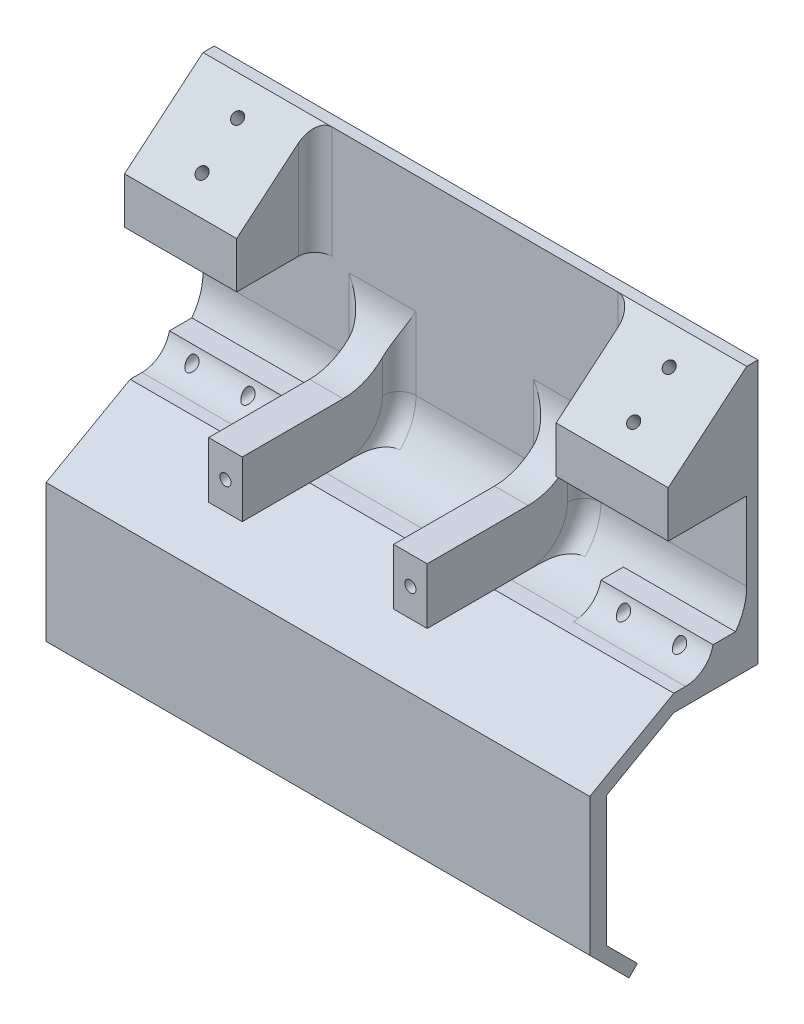
SolidWorks part; units mm, degrees
ref_plane "Front" through (0, 0, 0) normal (0, 0, 1) x (1, 0, 0)
ref_plane "Top" through (0, 0, 0) normal (0, 1, 0) x (1, 0, 0)
ref_plane "Right" through (0, 0, 0) normal (1, 0, 0) x (0, 0, -1)
sketch "Sketch1" plane through (0, 0, 0) normal (0, 0, 1) x (1, 0, 0)
  line L1 (0, 0) -> (97, 0)
  line L2 (0, 0) -> (0, 47)
  line L3 (0, 47) -> (97, 47)
  line L4 (97, 0) -> (97, 47)
  dimension "D1" = 97
  dimension "D2" = 47
extrude "Boss-Extrude1" add sketch "Sketch1" along normal blind 2
sketch "Sketch2" plane through (0, 0, 2) normal (0, 0, 1) x (1, 0, 0)
  line L0 (97, 0) -> (97, 47) construction
  line L1 (0, 47) -> (97, 47)
  line L2 (0, 47) -> (0, 27)
  line L3 (0, 27) -> (97, 27)
  line L4 (97, 47) -> (97, 27)
  dimension "D1" = 20
extrude "Boss-Extrude2" add sketch "Sketch2" along normal blind 20
sketch "Sketch3" plane through (0, 0, 0) normal (-1, 0, 0) x (0, 0, 1)
  line L0 (2, 47) -> (24.809, 27.8609)
  line L1 (22, 47) -> (0, 47) construction
  line L2 (24.809, 27.8609) -> (24.9418, 51.5997)
  line L3 (24.9418, 51.5997) -> (2, 47)
  line L5 (0, 47) -> (0, 0) construction
  dimension "D1" = 50
extrude "Cut-Extrude1" cut sketch "Sketch3" against normal blind 131
sketch "Sketch4" plane through (0, 0, 0) normal (-1, 0, 0) x (0, 0, 1)
  line L0 (19.0479, 32.6951) -> (21.146, 30.9346)
  line L1 (2, 47) -> (22, 30.218) construction
  line L2 (21.146, 30.9346) -> (25.8351, 27)
  line L3 (25.8351, 27) -> (20.0969, 27)
  line L4 (22, 27) -> (2, 27) construction
  line L5 (20.0969, 27) -> (19.0479, 32.6951)
extrude "Boss-Extrude3" add sketch "Sketch4" against normal up to surface (97 mm away) up to face at (97, 25.4597, 7.1429)
sketch "Sketch6" plane through (0, 0, 2) normal (0, 0, 1) x (1, 0, 0)
  line L0 (97, 47) -> (0, 47) construction
  line L1 (20, 47) -> (77, 47)
  line L2 (20, 47) -> (20, 18.3699)
  line L3 (20, 18.3699) -> (77, 18.3699)
  line L4 (77, 47) -> (77, 18.3699)
  line L5 (97, 47) -> (97, 27) construction
  line L6 (0, 47) -> (0, 27) construction
  dimension "D1" = 20
  dimension "D2" = 20
extrude "Cut-Extrude3" cut sketch "Sketch6" along normal blind 82
sketch "Sketch7" plane through (0, 0, 2) normal (0, 0, 1) x (1, 0, 0)
  line L0 (97, 0) -> (97, 27) construction
  line L1 (0, 0) -> (97, 0) construction
  circle A0 centre (15, 5) radius 1
  circle A1 centre (5, 5) radius 1
  circle A2 centre (92, 5) radius 1
  circle A3 centre (82, 5) radius 1
  dimension "D1" = 2
  dimension "D2" = 2
  dimension "D3" = 5
  dimension "D4" = 5
  dimension "D5" = 5
  dimension "D6" = 10
extrude "Cut-Extrude4" cut sketch "Sketch7" against normal blind 82
sketch "Sketch8" plane through (0, 0, 0) normal (-1, 0, 0) x (0, 0, 1)
  line L1 (16, 27) -> (34.739, 27)
  line L2 (16, 27) -> (16, 52.0421)
  line L3 (16, 52.0421) -> (34.739, 52.0421)
  line L4 (34.739, 27) -> (34.739, 52.0421)
  line L5 (2, 27) -> (2, 0) construction
  point P6 (0, 0)
  dimension "D1" = 14
extrude "Cut-Extrude5" cut sketch "Sketch8" against normal blind 136
sketch "Sketch9" plane through (0, 28.5655, 23.9693) normal (0, 0.766, 0.6428) x (1, 0, 0)
  line L0 (20, 28.6789) -> (0, 28.6789) construction
  line L1 (0, 10.4032) -> (20, 10.4032) construction
  circle A0 centre (10, 23.6789) radius 1
  circle A1 centre (10, 15.4032) radius 1
  circle A2 centre (87, 15.4032) radius 1
  circle A3 centre (87, 23.6789) radius 1
  point P12 (10, 28.6789)
  dimension "D3" = 2
  dimension "D4" = 2
  dimension "D1" = 5
  dimension "D2" = 5
extrude "Cut-Extrude6" cut sketch "Sketch9" against normal blind 6
sketch "Sketch11" plane through (0, 0, 2) normal (0, 0, 1) x (1, 0, 0)
  line L1 (0, 0) -> (97, 0)
  line L2 (0, 0) -> (0, 3)
  line L3 (0, 3) -> (97, 3)
  line L4 (97, 0) -> (97, 3)
  point P9 (97, 0)
  dimension "D1" = 3
extrude "Boss-Extrude4" add sketch "Sketch11" along normal blind 13
sketch "Sketch12" plane through (0, 0, 0) normal (-1, 0, 0) x (0, 0, 1)
  line L0 (15, 0) -> (27, -6.7563)
  line L1 (27, -6.7563) -> (32.3283, -6.7563)
  line L2 (32.3283, -6.7563) -> (15, 3)
  line L3 (15, 3) -> (15, 0)
  line L4 (0, 47) -> (0, 0) construction
  dimension "D1" = 27
extrude "Boss-Extrude5" add sketch "Sketch12" against normal up to vertex (97 mm away) up to point (97, 3, 2)
sketch "Sketch13" plane through (0, 0, 0) normal (-1, 0, 0) x (0, 0, 1)
  line L1 (27, -6.7563) -> (30, -6.7563)
  line L2 (27, -6.7563) -> (27, -30)
  line L3 (27, -30) -> (30, -30)
  line L4 (30, -6.7563) -> (30, -30)
  dimension "D1" = 3
  dimension "D2" = 30
extrude "Boss-Extrude6" add sketch "Sketch13" against normal up to vertex (97 mm away) up to point (97, 3, 15)
sketch "Sketch14" plane through (0, 0, 0) normal (-1, 0, 0) x (0, 0, 1)
  line L0 (30, -30) -> (30, -6.7563) construction
  line L1 (30, -11.4573) -> (34.8186, -11.4573)
  line L2 (30, -11.4573) -> (30, -0.9956)
  line L3 (30, -0.9956) -> (34.8186, -0.9956)
  line L4 (34.8186, -11.4573) -> (34.8186, -0.9956)
extrude "Cut-Extrude7" cut sketch "Sketch14" against normal up to vertex (97 mm away) up to point (97, 3, 15)
sketch "Sketch15" plane through (0, 0, 0) normal (-1, 0, 0) x (0, 0, 1)
  line L0 (30, -30) -> (23, -37)
  line L1 (23, -37) -> (21.5, -35.5)
  line L2 (21.5, -35.5) -> (27, -30)
  line L3 (27, -6.7563) -> (27, -30) construction
  line L4 (30, -30) -> (27, -30)
  line L17 (30, -30) -> (30, -5.4454)
  line L18 (30, -5.4454) -> (15, 3)
  line L19 (15, 3) -> (2, 3)
  line L20 (2, 3) -> (2, 27)
  line L21 (2, 27) -> (16, 27)
  line L22 (16, 27) -> (16, 35.2526)
  line L23 (16, 35.2526) -> (2, 47)
  line L24 (2, 47) -> (0, 47)
  line L25 (0, 47) -> (0, 0)
  line L26 (0, 0) -> (15, 0)
  line L27 (15, 0) -> (27, -6.7563)
  line L28 (27, -6.7563) -> (27, -30)
  line L29 (27, -30) -> (30, -30)
  line L30 (30, -30) -> (30, -5.4454)
  line L41 (27, -6.7563) -> (27, -30)
  line M29 (27, -30) -> (30, -30)
  dimension "D1" = 45
  dimension "D2" = 37
  dimension "D3" = 0
extrude "Boss-Extrude8" add sketch "Sketch15" against normal up to surface (97 mm away) contours L2 L1 L0 M29 region at (0, -33.14, 25.42) up to face at (97, 9.0039, 14)
sketch "Sketch16" plane through (0, 0, 2) normal (0, 0, 1) x (1, 0, 0)
  line L0 (97, 3) -> (0, 3) construction
  line L1 (62, 6) -> (68, 6)
  line L2 (62, 6) -> (62, 16)
  line L3 (62, 16) -> (68, 16)
  line L4 (68, 6) -> (68, 16)
  line L5 (48.5, 47) -> (48.5, 39.5123)
  line L6 (77, 47) -> (20, 47) construction
  line L7 (29, 6) -> (29, 16)
  line L8 (35, 16) -> (29, 16)
  line L9 (35, 6) -> (35, 16)
  line L10 (35, 6) -> (29, 6)
  point P7 (48.5, 3)
  dimension "D1" = 13.5
  dimension "D2" = 6
  dimension "D3" = 10
  dimension "D4" = 3
extrude "Boss-Extrude9" add sketch "Sketch16" along normal up to surface (28 mm away) contours L10 L9 L8 L7 | L1 L4 L3 L2 region at (65, 11, 2) region at (32, 11, 2) up to face at (48.5, -17.7227, 30)
sketch "Sketch17" plane through (0, 0, 30) normal (0, 0, 1) x (1, 0, 0)
  line L0 (35, 16) -> (29, 16) construction
  line L1 (35, 16) -> (29, 16) construction
  line L3 (62, 16) -> (68, 16) construction
  line L4 (62, 6) -> (62, 16) construction
  circle A0 centre (32, 11) radius 1
  circle A1 centre (65, 11) radius 1
  point P4 (0, 0)
  point P7 (0, 0)
  point P10 (32, 16)
  point P11 (0, 0)
  point P16 (65, 16)
  point P17 (62, 11)
  dimension "D2" = 2
  dimension "D3" = 2
  dimension "D1" = 5
extrude "Cut-Extrude8" cut sketch "Sketch17" against normal blind 8
sketch "Sketch18" plane through (0, 0, 2) normal (0, 0, 1) x (1, 0, 0)
  line L0 (0, 27) -> (0, 3) construction
  line L1 (0, 7) -> (20, 7)
  line L2 (0, 7) -> (0, 3)
  line L3 (0, 3) -> (20, 3)
  line L4 (20, 7) -> (20, 3)
  line L5 (97, 3) -> (0, 3) construction
  line L6 (48.5, 3) -> (48.5, 21.9576)
  line L7 (97, 3) -> (0, 3) construction
  line L8 (77, 7) -> (77, 3)
  line L9 (97, 3) -> (77, 3)
  line L10 (97, 7) -> (97, 3)
  line L11 (97, 7) -> (77, 7)
  circle A0 centre (5, 5) radius 1
  circle A1 centre (15, 5) radius 1
  circle A2 centre (82, 5) radius 1
  circle A3 centre (92, 5) radius 1
  circle M12 centre (92, 5) radius 1
  circle M13 centre (5, 5) radius 1
  circle M14 centre (15, 5) radius 1
  circle M15 centre (82, 5) radius 1
  line M16 (0, 3) -> (97, 3)
  line M17 (97, 3) -> (97, 27)
  line M23 (0, 27) -> (0, 3)
  dimension "D1" = 20
  dimension "D2" = 4
extrude "Boss-Extrude10" add sketch "Sketch18" along normal blind 6 contours L4 L1 M23 M16 M13 M14 | L11 L8 M17 M16 M15 M12 region at (87, 5, 2) region at (10, 5, 2)
fillet "Fillet1" radius 5 2 edges at (87, 3, 8) (10, 3, 8)
fillet "Fillet2" radius 10 3 edges at (48.5, 3, 2) (65, 16, 2) (32, 16, 2)
fillet "Fillet3" radius 3 4 edges at (35, 19.5, 2) (62, 19.5, 2) (35, 9.2194, 2.7422) (62, 9.2194, 2.7422)
fillet "Fillet4" radius 3 4 edges at (68, 19.5, 2) (29, 19.5, 2) (68, 9.2194, 2.7422) (29, 9.2194, 2.7422)
fillet "Fillet5" radius 3 2 edges at (20, 37, 2) (77, 37, 2)
